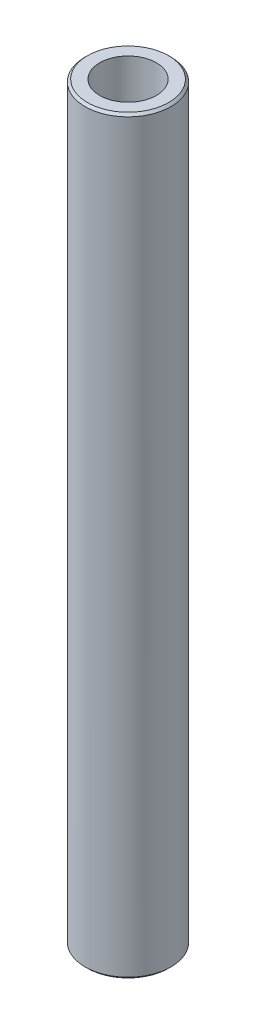
SolidWorks part; units mm, degrees
ref_plane "Front Plane" through (0, 0, 0) normal (0, 0, 1) x (1, 0, 0)
ref_plane "Top Plane" through (0, 0, 0) normal (0, 1, 0) x (1, 0, 0)
ref_plane "Right Plane" through (0, 0, 0) normal (1, 0, 0) x (0, 0, -1)
sketch "Sketch1" plane through (0, 0, 0) normal (0, 1, 0) x (1, 0, 0)
  circle A0 centre (0, 0) radius 27.5
  dimension "SHAFT_OD" = 55
extrude "Boss-Extrude1" add sketch "Sketch1" along normal blind 480.0797
sketch "Sketch2" plane through (0, 0, 0) normal (0, 1, 0) x (1, 0, 0)
  circle A0 centre (0, 0) radius 18.1618
  dimension "BORE_D" = 36.3236
extrude "Cut-Extrude1" cut sketch "Sketch2" along normal through all
chamfer "Chamfer1" distance 1.5101 angle 45 2 edges at (0, 480.0797, 27.5) (0, 0, 27.5)
